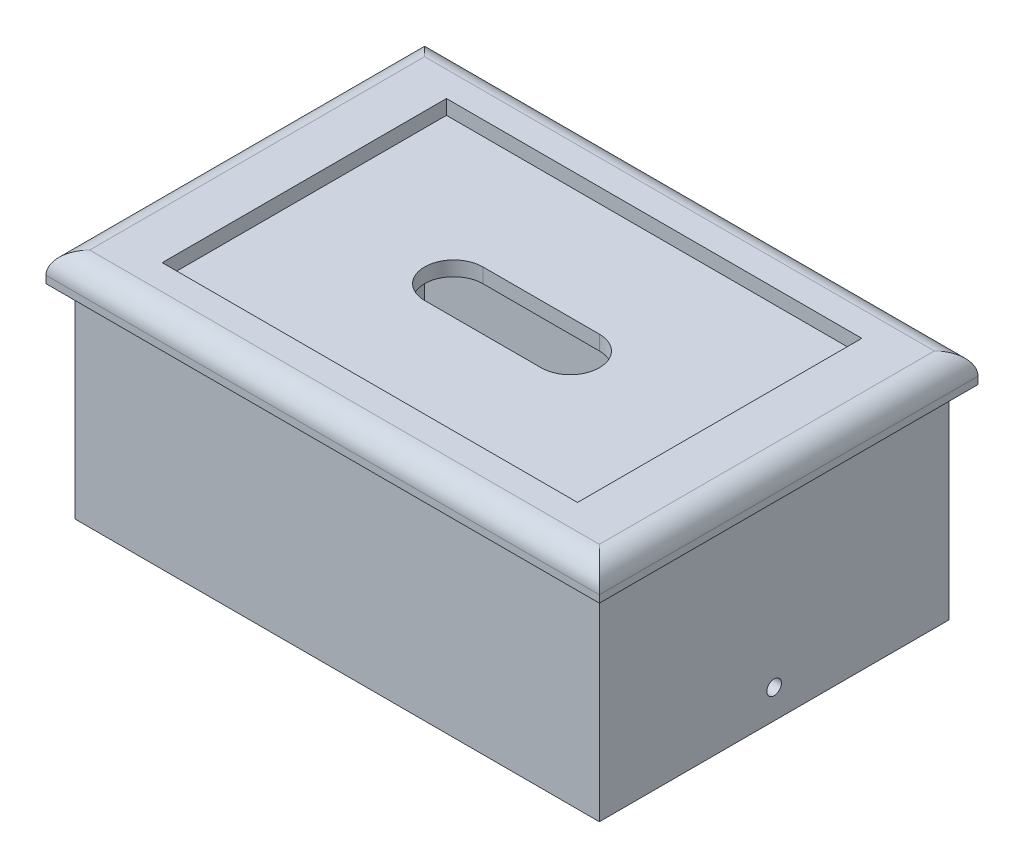
SolidWorks part; units mm, degrees
ref_plane "Front Plane" through (0, 0, 0) normal (0, 0, 1) x (1, 0, 0)
ref_plane "Top Plane" through (0, 0, 0) normal (0, 1, 0) x (1, 0, 0)
ref_plane "Right Plane" through (0, 0, 0) normal (1, 0, 0) x (0, 0, -1)
sketch "Sketch1" plane through (0, 0, 0) normal (0, 1, 0) x (1, 0, 0)
  line L0 (60.325, 41.275) -> (-60.325, 41.275)
  line L1 (57.15, -38.1) -> (-57.15, -38.1) construction
  line L2 (57.15, -38.1) -> (57.15, 38.1) construction
  line L3 (57.15, 38.1) -> (-57.15, 38.1) construction
  line L4 (-57.15, -38.1) -> (-57.15, 38.1) construction
  line L5 (57.15, -38.1) -> (-57.15, 38.1) construction
  line L6 (57.15, 38.1) -> (-57.15, -38.1) construction
  line L7 (-60.325, -41.275) -> (-60.325, 41.275)
  line L8 (60.325, -41.275) -> (-60.325, -41.275)
  line L9 (60.325, -41.275) -> (60.325, 41.275)
  point P0 (0, 0)
  dimension "D1" = 76.2
  dimension "D2" = 114.3
  dimension "D3" = 3.175
extrude "MainBody" add sketch "Sketch1" along normal blind 50.8
sketch "Sketch2" plane through (0, 50.8, 0) normal (0, 1, 0) x (1, 0, 0)
  line L0 (-45.2763, -30.9888) -> (-45.2763, 30.9888)
  line L1 (44.45, -30.1625) -> (-44.45, -30.1625) construction
  line L2 (44.45, -30.1625) -> (44.45, 30.1625) construction
  line L3 (44.45, 30.1625) -> (-44.45, 30.1625) construction
  line L4 (-44.45, -30.1625) -> (-44.45, 30.1625) construction
  line L5 (44.45, -30.1625) -> (-44.45, 30.1625) construction
  line L6 (44.45, 30.1625) -> (-44.45, -30.1625) construction
  line L7 (45.2763, 30.9888) -> (-45.2763, 30.9888)
  line L8 (45.2763, -30.9888) -> (45.2763, 30.9888)
  line L9 (45.2763, -30.9888) -> (-45.2763, -30.9888)
  point P0 (0, 0)
  dimension "D1" = 60.325
  dimension "D2" = 88.9
  dimension "D3" = 0.8263
extrude "SolarPanelRecess" cut sketch "Sketch2" against normal blind 3.175
sketch "Sketch3" plane through (0, 47.625, 0) normal (0, 1, 0) x (1, 0, 0)
  line L0 (-12.7, 0) -> (12.7, 0) construction
  line L1 (-12.7, 6.35) -> (12.7, 6.35)
  line L2 (-12.7, -6.35) -> (12.7, -6.35)
  arc A0 (-12.7, 6.35) -> (-12.7, -6.35) centre (-12.7, 0) ccw
  arc A1 (12.7, -6.35) -> (12.7, 6.35) centre (12.7, 0) ccw
  point P2 (0, 0)
  dimension "D2" = 6.35
  dimension "D1" = 25.4
extrude "SolarPanelWiringRecess" cut sketch "Sketch3" against normal through all
sketch "Sketch4" plane through (0, 0, 0) normal (0, -1, 0) x (1, 0, 0)
  line L0 (-63.5, -44.45) -> (63.5, -44.45)
  line L1 (52.3875, -33.3375) -> (-52.3875, -33.3375)
  line L2 (52.3875, -33.3375) -> (52.3875, 33.3375)
  line L3 (52.3875, 33.3375) -> (-52.3875, 33.3375)
  line L4 (-52.3875, -33.3375) -> (-52.3875, 33.3375)
  line L5 (52.3875, -33.3375) -> (-52.3875, 33.3375) construction
  line L6 (52.3875, 33.3375) -> (-52.3875, -33.3375) construction
  line L7 (-57.15, 38.1) -> (57.15, 38.1)
  line L8 (-57.15, 38.1) -> (-57.15, -38.1)
  line L9 (-57.15, -38.1) -> (57.15, -38.1)
  line L10 (57.15, 38.1) -> (57.15, -38.1)
  line L11 (-57.15, 38.1) -> (57.15, -38.1) construction
  line L12 (-57.15, -38.1) -> (57.15, 38.1) construction
  line L13 (63.5, 44.45) -> (63.5, -44.45)
  line L14 (-63.5, 44.45) -> (63.5, 44.45)
  line L15 (-63.5, 44.45) -> (-63.5, -44.45)
  point P0 (0, 0)
  point P6 (0, 0)
  line M3 (12.7, -6.35) -> (-12.7, -6.35)
  arc M4 (-12.7, -6.35) -> (-12.7, 6.35) centre (-12.7, 0) cw
  line M5 (-12.7, 6.35) -> (12.7, 6.35)
  arc M6 (12.7, 6.35) -> (12.7, -6.35) centre (12.7, 0) cw
  line M13 (60.325, -41.275) -> (60.325, 41.275)
  line M14 (60.325, 41.275) -> (-60.325, 41.275)
  line M15 (-60.325, 41.275) -> (-60.325, -41.275)
  line M16 (-60.325, -41.275) -> (60.325, -41.275)
  dimension "D1" = 66.675
  dimension "D2" = 104.775
  dimension "D3" = 114.3
  dimension "D4" = 76.2
  dimension "D5" = 6.35
extrude "InsideEnclosureRecess_OutsideFlange" cut sketch "Sketch4" against normal offset from surface (44.45 mm away) 3.175 contours L14 L15 L0 L13 M13 M16 M15 M14 | L7 L10 L9 L8 M16 M13 M14 M15 | L4 L1 L2 L3 M6 M3 M4 M5 region at (-61.9498, 0, 0) region at (0, 0, -32.0956) region at (0, 0, -39.8131) up to face at (0, 47.625, 0)
fillet "Fillet1" radius 4.7625 4 edges at (60.325, 50.8, 0) (0, 50.8, 41.275) (-60.325, 50.8, 0) (0, 50.8, -41.275)
sketch "Sketch6" plane through (-57.15, 0, 0) normal (-1, 0, 0) x (0, 0, 1)
  line L1 (-14.2875, 25.4) -> (14.2875, 25.4) construction
  line L2 (-14.2875, 24.6063) -> (14.2875, 24.6063)
  line L3 (14.2875, 24.6063) -> (26.9875, 24.6063)
  line L4 (26.9875, 24.6063) -> (26.9875, 11.9063)
  line L5 (26.9875, 11.9063) -> (-23.8125, 11.9062)
  line L6 (-23.8125, 11.9062) -> (-23.8125, 24.6063)
  line L7 (-23.8125, 24.6063) -> (-14.2875, 24.6063)
  dimension "D2" = 6.35
  dimension "D3" = 9.525
  dimension "D4" = 12.7
  dimension "D1" = 0.7937
extrude "CableAccess" cut sketch "Sketch6" against normal up to next
sketch "Sketch9" plane through (57.15, 0, 0) normal (1, 0, 0) x (0, 0, -1)
  line L0 (0, 0) -> (0, 6.35) construction
  line L1 (-38.1, 0) -> (38.1, 0) construction
  circle A0 centre (0, 6.35) radius 1.5875
  dimension "D1" = 3.175
  dimension "D2" = 6.35
extrude "TopEdgeHoles" cut sketch "Sketch9" against normal through all
sketch "Sketch10" plane through (0, 44.45, 0) normal (0, -1, 0) x (1, 0, 0)
  line L0 (-52.3875, 33.3375) -> (-52.3875, -33.3375) construction
  line L1 (50.0062, 31.75) -> (-50.0063, 31.75) construction
  line L2 (50.0062, 31.75) -> (50.0062, -31.75) construction
  line L3 (50.0062, -31.75) -> (-50.0063, -31.75) construction
  line L4 (-50.0063, 31.75) -> (-50.0063, -31.75) construction
  line L5 (50.0062, 31.75) -> (-50.0063, -31.75) construction
  line L6 (50.0062, -31.75) -> (-50.0063, 31.75) construction
  line L7 (-52.3875, 33.3375) -> (52.3875, 33.3375) construction
  line L8 (-52.3875, 33.3375) -> (-52.3875, 23.8125)
  line L9 (-52.3875, 33.3375) -> (-42.8625, 33.3375)
  line L10 (-42.8625, 33.3375) -> (52.3875, 33.3375) construction
  line L11 (-52.3875, 23.8125) -> (-52.3875, -33.3375) construction
  line L12 (-52.3875, -33.3375) -> (52.3875, -33.3375) construction
  arc A0 (-52.3875, 23.8125) -> (-42.8625, 33.3375) centre (-52.3875, 33.3375) ccw
  arc A1 (-42.8625, 33.3375) -> (-52.3875, 23.8125) centre (-52.3875, 33.3375) ccw construction
  circle A2 centre (-52.3875, -33.3375) radius 9.525
  circle A3 centre (52.3875, -33.3375) radius 9.525
  circle A4 centre (52.3875, 33.3375) radius 9.525
  point P0 (0, 0)
  line M12 (52.3875, 33.3375) -> (-52.3875, 33.3375)
  line M13 (-52.3875, 33.3375) -> (-52.3875, -33.3375)
  line M14 (-52.3875, -33.3375) -> (52.3875, -33.3375)
  line M15 (52.3875, -33.3375) -> (52.3875, 33.3375)
  dimension "D3" = 19.05
  dimension "D1" = 63.5
  dimension "D2" = 100.0125
extrude "CornerStandoffs" add sketch "Sketch10" along normal blind 15.875 contours A0 M13 M12 | A4 M12 M15 | A2 M14 M13 | A3 M15 M14 region at (-48.345, 44.45, 29.295) region at (-48.345, 44.45, -29.295) region at (48.345, 44.45, 29.295) region at (48.345, 44.45, -29.295)
sketch "Sketch11" plane through (0, 28.575, 0) normal (0, -1, 0) x (1, 0, 0)
  line L0 (50.0062, 31.75) -> (-50.0063, 31.75) construction
  line L1 (-50.0063, 31.75) -> (-50.0063, -31.75) construction
  line L2 (50.0062, -31.75) -> (-50.0063, -31.75) construction
  line L3 (50.0062, 31.75) -> (50.0062, -31.75) construction
  line L4 (50.0062, 31.75) -> (-50.0063, 31.75) construction
  line L5 (-50.0063, 31.75) -> (-50.0063, -31.75) construction
  line L6 (50.0062, -31.75) -> (-50.0063, -31.75) construction
  line L7 (50.0062, 31.75) -> (50.0062, -31.75) construction
  line L8 (46.8312, 28.575) -> (46.8312, -28.575) construction
  line L9 (46.8312, -28.575) -> (-46.8313, -28.575) construction
  line L10 (-46.8313, 28.575) -> (-46.8313, -28.575) construction
  line L11 (46.8312, 28.575) -> (-46.8313, 28.575) construction
  circle A0 centre (46.8312, -28.575) radius 1.143
  circle A1 centre (-46.8313, -28.575) radius 1.143
  circle A2 centre (-46.8313, 28.575) radius 1.143
  circle A3 centre (46.8312, 28.575) radius 1.143
  dimension "D2" = 2.286
  dimension "D1" = 3.175
extrude "ScrewStandoffHoles" cut sketch "Sketch11" against normal blind 6.35
sketch "Sketch12" plane through (0, 0, 0) normal (0, -1, 0) x (1, 0, 0)
  line L4 (53.975, -34.925) -> (53.975, 34.925)
  line L5 (53.975, 34.925) -> (-53.975, 34.925)
  line L6 (-53.975, 34.925) -> (-53.975, -34.925)
  line L7 (-53.975, -34.925) -> (53.975, -34.925)
  line L8 (55.5625, -36.5125) -> (55.5625, 36.5125)
  line L9 (55.5625, 36.5125) -> (-55.5625, 36.5125)
  line L10 (-55.5625, 36.5125) -> (-55.5625, -36.5125)
  line L11 (-55.5625, -36.5125) -> (55.5625, -36.5125)
  line L12 (55.5625, -36.5125) -> (55.5625, 36.5125)
  line L13 (55.5625, 36.5125) -> (-55.5625, 36.5125)
  line L14 (-55.5625, 36.5125) -> (-55.5625, -36.5125)
  line L15 (-55.5625, -36.5125) -> (55.5625, -36.5125)
  dimension "D1" = 1.5875
  dimension "D2" = 1.5875
extrude "Cut-Extrude5" cut sketch "Sketch12" against normal blind 3.175
